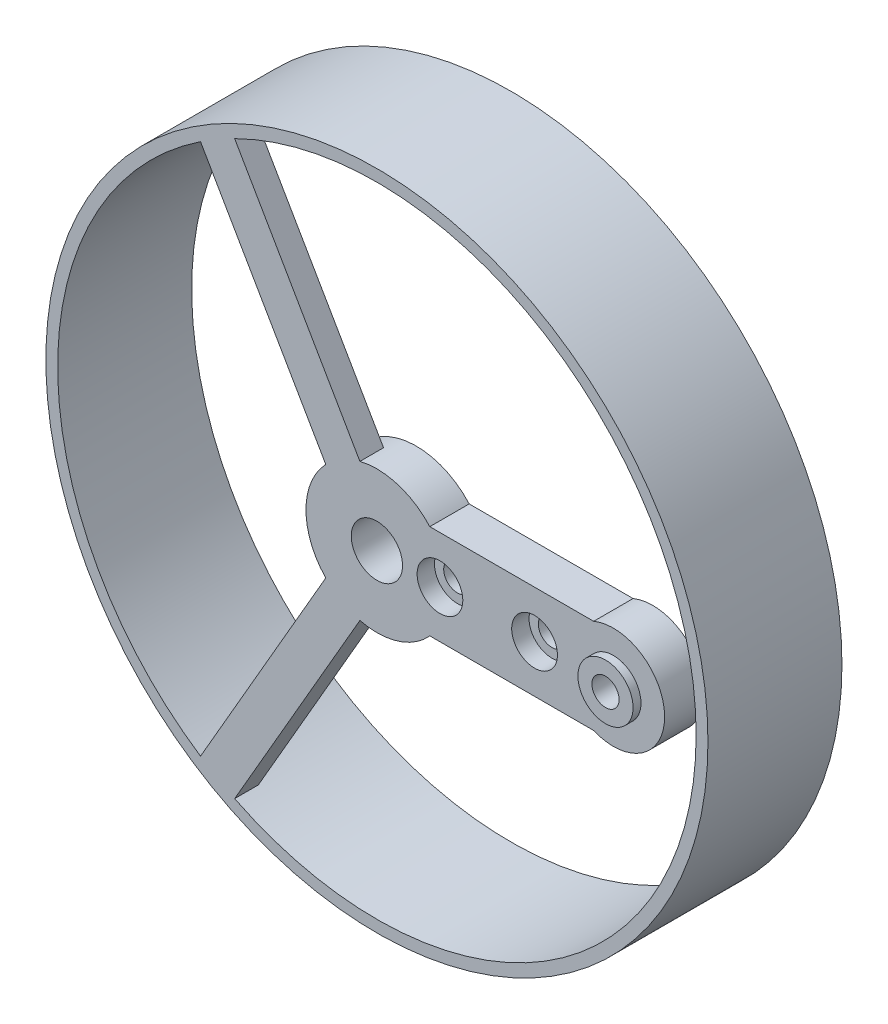
SolidWorks part; units mm, degrees
ref_plane "Front Plane" through (0, 0, 0) normal (0, 0, 1) x (1, 0, 0)
ref_plane "Top Plane" through (0, 0, 0) normal (0, 1, 0) x (1, 0, 0)
ref_plane "Right Plane" through (0, 0, 0) normal (1, 0, 0) x (0, 0, -1)
sketch "Sketch1" plane through (0, 0, 0) normal (0, 0, 1) x (1, 0, 0)
  line L0 (0, -6) -> (30, -6)
  line L1 (30, -6) -> (30, 6)
  line L2 (30, 6) -> (0, 6)
  line L3 (0, 6) -> (0, -6)
extrude "Boss-Extrude1" add sketch "Sketch1" along normal blind 5 from offset 9 offset against normal yes
sketch "Sketch2" plane through (0, 0, 0) normal (0, 0, 1) x (1, 0, 0)
  circle A0 centre (0, 0) radius 9
extrude "Boss-Extrude2" add sketch "Sketch2" along normal blind 5 from offset 9 offset against normal yes
sketch "Sketch3" plane through (0, 0, 0) normal (0, 0, 1) x (1, 0, 0)
  circle A0 centre (30, 0) radius 6.5
extrude "Boss-Extrude3" add sketch "Sketch3" along normal blind 5 from offset 9 offset against normal yes
sketch "Sketch4" plane through (0, 0, 0) normal (0, 0, 1) x (1, 0, 0)
  circle A0 centre (0, 0) radius 3.25
extrude "Cut-Extrude1" cut sketch "Sketch4" against normal through all and the other way through all
sketch "Sketch5" plane through (0, 0, 0) normal (0, 0, 1) x (1, 0, 0)
  circle A0 centre (8, 0) radius 1.725
  circle A1 centre (20, 0) radius 1.725
  circle A2 centre (30, 0) radius 1.725
extrude "Cut-Extrude2" cut sketch "Sketch5" against normal through all and the other way through all
sketch "Sketch6" plane through (0, 0, 0) normal (0, 0, 1) x (1, 0, 0)
  circle A0 centre (8, 0) radius 2.9
extrude "Cut-Extrude3" cut sketch "Sketch6" along normal blind 2.2 from offset 6.2 offset against normal yes
sketch "Sketch7" plane through (0, 0, 0) normal (0, 0, 1) x (1, 0, 0)
  circle A0 centre (20, 0) radius 2.9
extrude "Cut-Extrude4" cut sketch "Sketch7" along normal blind 2.2 from offset 6.2 offset against normal yes
sketch "Sketch8" plane through (0, 0, 0) normal (0, 0, 1) x (1, 0, 0)
  circle A0 centre (30, 0) radius 2.9
extrude "Cut-Extrude5" cut sketch "Sketch8" along normal blind 2.2 from offset 9 offset against normal yes
sketch "Sketch9" plane through (0, 0, 0) normal (0, 0, 1) x (1, 0, 0)
  circle A0 centre (30, 0) radius 3.5
extrude "Boss-Extrude4" add sketch "Sketch9" along normal blind 1 from offset 4 offset against normal yes
sketch "Sketch10" plane through (0, 0, 0) normal (0, 0, 1) x (1, 0, 0)
  circle A0 centre (30, 0) radius 1.725
extrude "Cut-Extrude6" cut sketch "Sketch10" against normal through all and the other way through all
sketch "Sketch11" plane through (0, 0, 0) normal (0, 0, 1) x (1, 0, 0)
  circle A0 centre (0, 0) radius 42
  circle A1 centre (0, 0) radius 40.5
extrude "Boss-Extrude5" add sketch "Sketch11" along normal blind 17 from offset 21 offset against normal yes
sketch "Sketch12" plane through (0, 0, 0) normal (0, 0, 1) x (1, 0, 0)
  line L0 (-1.3349, 7.3122) -> (-18.5849, 37.1901)
  line L1 (-18.5849, 37.1901) -> (-22.9151, 34.6901)
  line L2 (-22.9151, 34.6901) -> (-5.6651, 4.8122)
  line L3 (-5.6651, 4.8122) -> (-1.3349, 7.3122)
  line L4 (-5.6651, -4.8122) -> (-22.9151, -34.6901)
  line L5 (-22.9151, -34.6901) -> (-18.5849, -37.1901)
  line L6 (-18.5849, -37.1901) -> (-1.3349, -7.3122)
  line L7 (-1.3349, -7.3122) -> (-5.6651, -4.8122)
extrude "Boss-Extrude6" add sketch "Sketch12" along normal blind 3 from offset 7 offset against normal yes
